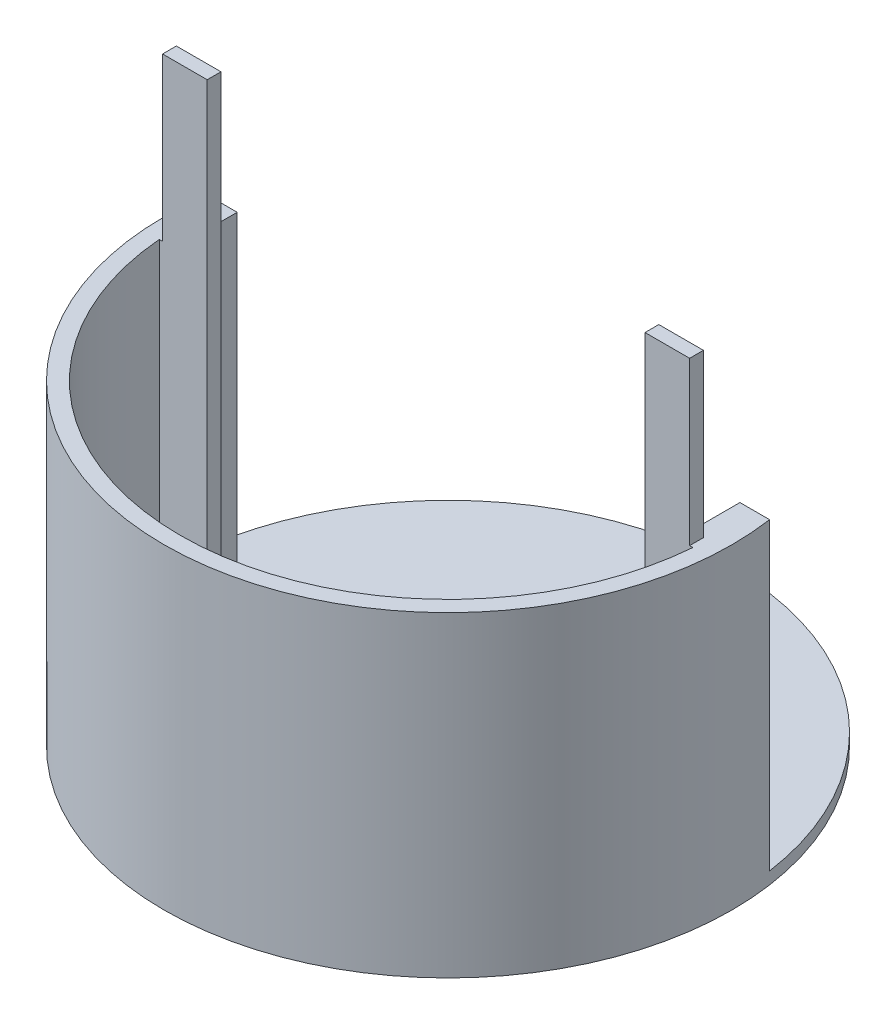
SolidWorks part; units mm, degrees
material "ABS"
ref_plane "Front Plane" through (0, 0, 0) normal (0, 0, 1) x (1, 0, 0)
ref_plane "Top Plane" through (0, 0, 0) normal (0, 1, 0) x (1, 0, 0)
ref_plane "Right Plane" through (0, 0, 0) normal (1, 0, 0) x (0, 0, -1)
sketch "Sketch1" plane through (0, 0, 0) normal (0, 1, 0) x (1, 0, 0)
  line L0 (-27, -7.4) -> (27, -7.4) construction
  circle A0 centre (0, 0) radius 35
  circle A1 centre (-27, -7.4) radius 2.75
  circle A2 centre (27, -7.4) radius 2.75
  point P7 (0, -7.4)
  dimension "D2" = 5.5
  dimension "D3" = 70
  dimension "D1" = 54
  dimension "D4" = 7.4
extrude "Boss-Extrude1" add sketch "Sketch1" along normal blind 1.5
sketch "Sketch2" plane through (0, 1.5, 0) normal (0, 1, 0) x (1, 0, 0)
  line L0 (-32.9848, -1) -> (-34.9857, -1) construction
  line L2 (-30.9853, -1) -> (-26.9848, -1)
  line L3 (-26.9848, -1) -> (-26.9848, -2.7)
  line L4 (-26.9848, -2.7) -> (-32.8894, -2.7)
  line L5 (30.9853, -1) -> (26.9848, -1)
  line L6 (26.9848, -1) -> (26.9848, -2.7)
  line L7 (26.9848, -2.7) -> (32.8894, -2.7)
  line L8 (30.9853, -1) -> (30.9853, 5)
  line L9 (30.9853, 5) -> (34.641, 5)
  line L10 (-34.641, 5) -> (-30.9853, 5)
  line L11 (-30.9853, 5) -> (-30.9853, -1)
  line L12 (-32.9848, -1) -> (-30.9853, -1) construction
  line L13 (34.9857, -1) -> (30.9853, -1) construction
  circle A0 centre (0, 0) radius 35 construction
  arc A1 (-34.9857, -1) -> (34.9857, -1) centre (0, 0) ccw
  arc A2 (-32.8894, -2.7) -> (32.8894, -2.7) centre (0, 0) ccw
  arc A3 (34.9857, -1) -> (34.641, 5) centre (0, 0) ccw
  circle A4 centre (0, 0) radius 35 construction
  arc A5 (34.641, 5) -> (-34.641, 5) centre (0, 0) ccw construction
  circle A6 centre (0, 0) radius 33 construction
  arc A7 (-32.9848, -1) -> (-32.8894, -2.7) centre (0, 0) ccw construction
  arc A8 (-34.641, 5) -> (-34.9857, -1) centre (0, 0) ccw
  point P17 (0, 0)
  dimension "D2" = 1
  dimension "D3" = 1.7
  dimension "D4" = 6
  dimension "D5" = 6
  dimension "D1" = 2
extrude "Boss-Extrude2" add sketch "Sketch2" along normal blind 37.5
sketch "Sketch3" plane through (0, 39, 0) normal (0, 1, 0) x (1, 0, 0)
  line L0 (-32.8894, -2.7) -> (-26.9848, -2.7) construction
  line L1 (-26.9848, -1) -> (-32.4848, -1)
  line L2 (-26.9848, -1) -> (-26.9848, -2.7)
  line L3 (-26.9848, -2.7) -> (-32.4848, -2.7)
  line L4 (-32.4848, -1) -> (-32.4848, -2.7)
  line L5 (-26.9848, -1) -> (-32.4848, -2.7) construction
  line L6 (-26.9848, -2.7) -> (-32.4848, -1) construction
  line L7 (26.9848, -2.7) -> (32.8894, -2.7) construction
  line L8 (26.9848, -1) -> (32.4848, -1)
  line L9 (26.9848, -1) -> (26.9848, -2.7)
  line L10 (26.9848, -2.7) -> (32.4848, -2.7)
  line L11 (32.4848, -1) -> (32.4848, -2.7)
  line L12 (26.9848, -1) -> (32.4848, -2.7) construction
  line L13 (26.9848, -2.7) -> (32.4848, -1) construction
  point P4 (-29.7348, -1.85)
  point P12 (29.7348, -1.85)
  dimension "D1" = 5.5
extrude "Boss-Extrude3" add sketch "Sketch3" along normal blind 20
